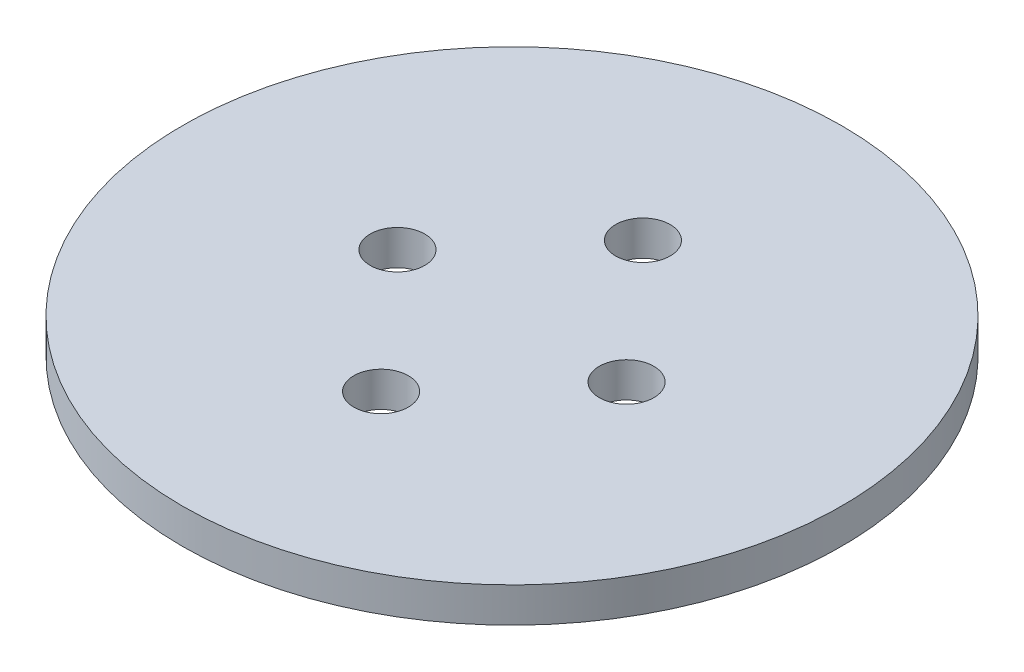
SolidWorks part; units mm, degrees
material "Pine"
ref_plane "Front Plane" through (0, 0, 0) normal (0, 0, 1) x (1, 0, 0)
ref_plane "Top Plane" through (0, 0, 0) normal (0, 1, 0) x (1, 0, 0)
ref_plane "Right Plane" through (0, 0, 0) normal (1, 0, 0) x (0, 0, -1)
sketch "Sketch1" plane through (0, 0, 0) normal (0, 1, 0) x (1, 0, 0)
  circle A0 centre (0, 0) radius 47.9552
  dimension "D1" = 95.9104
extrude "Boss-Extrude1" add sketch "Sketch1" along normal blind 5.08
hole_wizard "U-bolt Holes" positions "Sketch2" profile "Sketch3" tap size "5/16-18" standard "ANSI Inch" end condition through all
sketch "Sketch2" plane through (0, 5.08, 0) normal (0, 1, 0) x (1, 0, 0)
  line L0 (0, 0) -> (0, 20.4425) construction
  point P0 (-16.6687, 0)
  point P12 (16.6687, 0)
  dimension "D1" = 33.3375
sketch "Sketch3" plane through (-16.6687, 5.08, 0) normal (1, 0, 0) x (0, 0, 1)
  line L0 (0, 0) -> (0, 5.08)
  line L1 (0, 5.08) -> (3.9687, 5.08)
  line L2 (3.9687, 5.08) -> (3.9687, 0)
  line L5 (3.9687, 0) -> (0, 0)
  line L11 (0, -6.35) -> (0, 107.95) construction
  dimension "Thru Tap Drill Dia." = 7.9375
  dimension "Thru Tap Drill Depth" = 5.08
cosmetic thread "Hole Thread1" parameters "D2"=7.9375
cosmetic thread "Hole Thread2" parameters "D2"=7.9375
hole_wizard "Threaded Rod Holes" positions "Sketch4" profile "Sketch5" tap size "5/16-18" standard "ANSI Inch" end condition through all
sketch "Sketch4" plane through (0, 5.08, 0) normal (0, 1, 0) x (1, 0, 0)
  line L1 (0, 0) -> (0, -19.05) construction
  line L3 (0, 0) -> (0, 19.05) construction
  point P13 (0, -19.05)
  point P17 (0, 19.05)
  dimension "D1" = 38.1
sketch "Sketch5" plane through (0, 5.08, -19.05) normal (1, 0, 0) x (0, 0, 1)
  line L0 (0, 0) -> (0, 5.08)
  line L1 (0, 5.08) -> (3.9687, 5.08)
  line L2 (3.9687, 5.08) -> (3.9687, 0)
  line L5 (3.9687, 0) -> (0, 0)
  line L11 (0, -6.35) -> (0, 107.95) construction
  dimension "Thru Tap Drill Dia." = 7.9375
  dimension "Thru Tap Drill Depth" = 5.08
cosmetic thread "Hole Thread3" parameters "D2"=7.9375
cosmetic thread "Hole Thread4" parameters "D2"=7.9375
